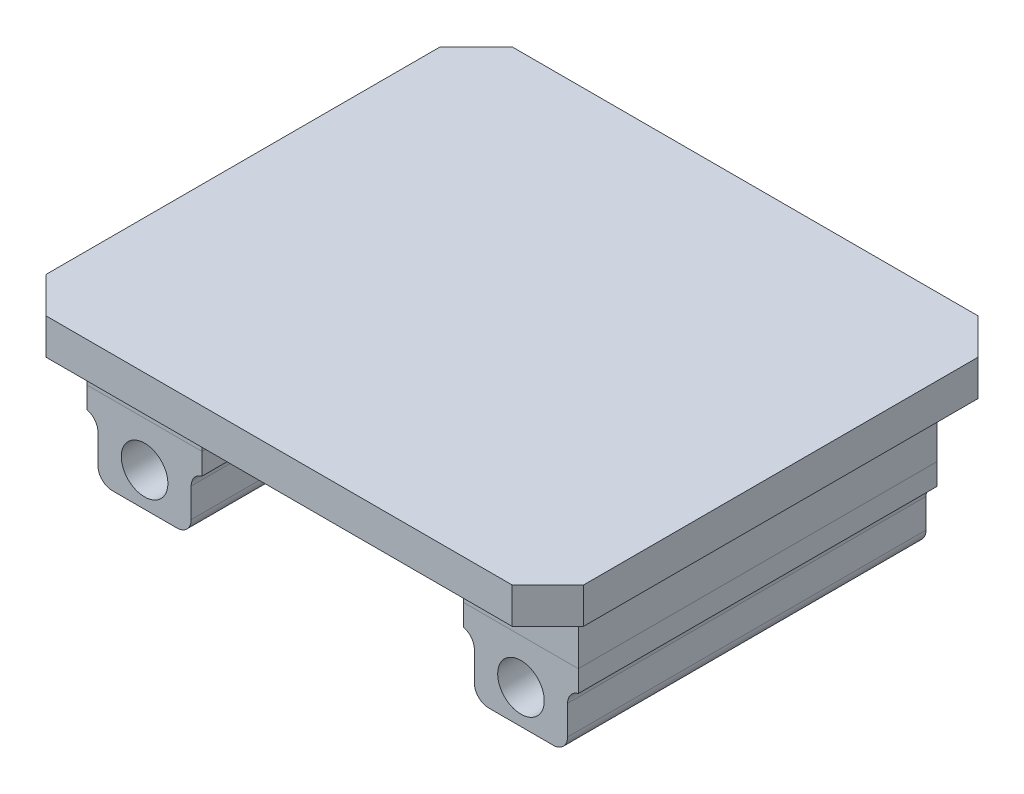
SolidWorks part; units mm, degrees
ref_plane "Front Plane" through (0, 0, 0) normal (0, 0, 1) x (1, 0, 0)
ref_plane "Top Plane" through (0, 0, 0) normal (0, 1, 0) x (1, 0, 0)
ref_plane "Right Plane" through (0, 0, 0) normal (1, 0, 0) x (0, 0, -1)
sketch "Sketch1" plane through (0, 0, 0) normal (0, 0, 1) x (1, 0, 0)
  line L0 (-52.5, 0) -> (52.5, 0) construction
  line L1 (-39.5, -9.5) -> (-65.5, -9.5)
  line L2 (-65.5, -9.5) -> (-65.5, 6.5)
  line L3 (-65.5, 6.5) -> (-68.5, 6.5)
  line L4 (-68.5, 6.5) -> (-68.5, 12.5)
  line L5 (-68.5, 12.5) -> (-36.5, 12.5)
  line L6 (-36.5, 12.5) -> (-36.5, 6.5)
  line L7 (-36.5, 6.5) -> (-39.5, 6.5)
  line L8 (-39.5, 6.5) -> (-39.5, -9.5)
  circle A0 centre (-52.5, 0) radius 6.5
  point P4 (0, 0)
  point P6 (0, 0)
  point P15 (-39.0787, -9.8749)
  dimension "D2" = 13
  dimension "D1" = 105
  dimension "D3" = 13
  dimension "D4" = 13
  dimension "D5" = 3
  dimension "D7" = 22
  dimension "6" = 6
extrude "Boss-Extrude1" add sketch "Sketch1" along normal mid plane 100
sketch "Sketch2" plane through (0, 12.5, 0) normal (0, 1, 0) x (1, 0, 0)
  line L4 (-36.5, 50) -> (-68.5, 50)
  line L5 (-68.5, 50) -> (-68.5, -50)
  line L6 (-68.5, -50) -> (-36.5, -50)
  line L7 (-36.5, -50) -> (-36.5, 50)
  line L8 (-36.5, 50) -> (-68.5, 50)
  line L9 (-68.5, 50) -> (-68.5, -50)
  line L10 (-68.5, -50) -> (-36.5, -50)
  line L11 (-36.5, -50) -> (-36.5, 50)
  dimension "D1" = 0
extrude "Boss-Extrude2" add sketch "Sketch2" along normal blind 16 separate body
mirror "Mirror5" about plane through (0, 0, 0) normal (1, 0, 0) of bodies 103 101
sketch "Sketch5" plane through (0, 28.5, 0) normal (0, 1, 0) x (1, 0, 0)
  line L1 (-75, 65) -> (75, 65)
  line L2 (-75, 65) -> (-75, -65)
  line L3 (-75, -65) -> (75, -65)
  line L4 (75, 65) -> (75, -65)
  line L5 (-75, 65) -> (75, -65) construction
  line L6 (-75, -65) -> (75, 65) construction
  point P0 (0, 0)
  dimension "D1" = 150
  dimension "D2" = 130
extrude "Boss-Extrude3" add sketch "Sketch5" along normal blind 10 separate body
chamfer "Chamfer1" distance 10 angle 45 4 edges at (-75, 33.5, -65) (75, 33.5, -65) (75, 33.5, 65) (-75, 33.5, 65)
fillet "Fillet1" radius 4 4 edges at (-39.5, 6.5, 0) (-65.5, 6.5, 0) (-39.5, -9.5, 0) (-65.5, -9.5, 0)
fillet "Fillet2" radius 4 4 edges at (65.5, 6.5, 0) (65.5, -9.5, 0) (39.5, 6.5, 0) (39.5, -9.5, 0)
